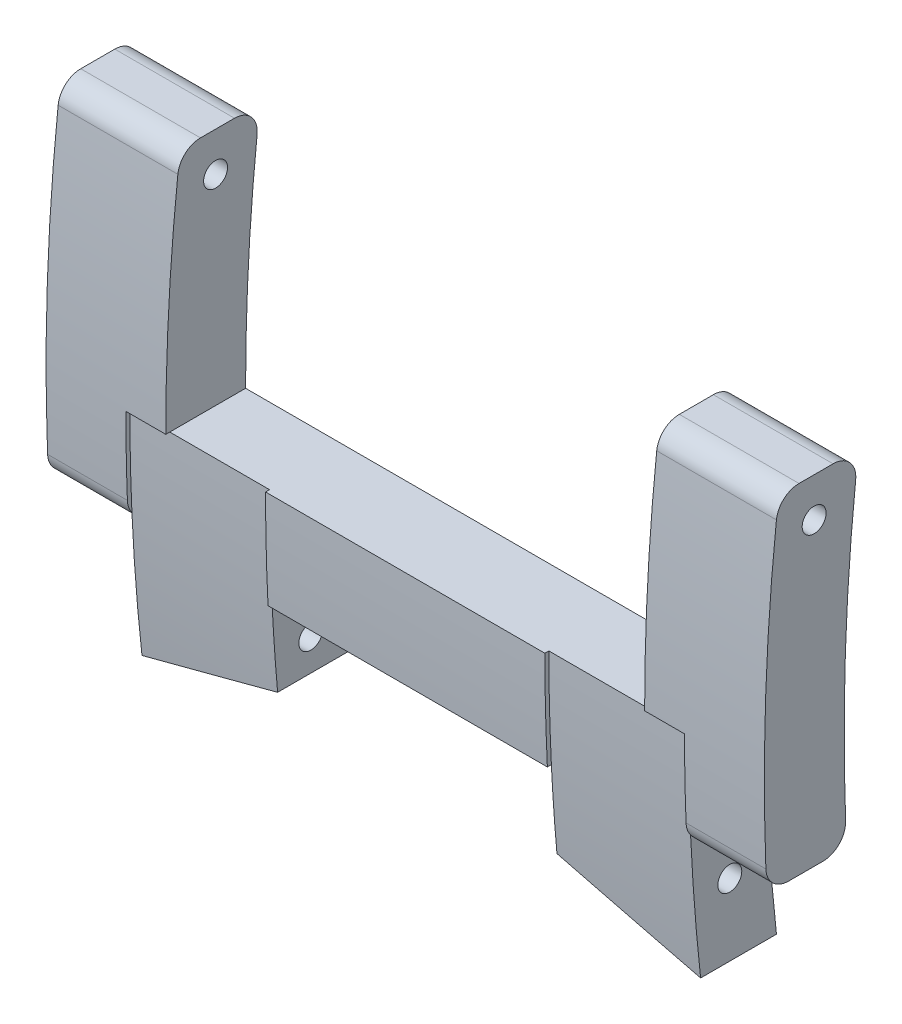
SolidWorks part; units mm, degrees
ref_plane "Front Plane" through (0, 0, 0) normal (0, 0, 1) x (1, 0, 0)
ref_plane "Top Plane" through (0, 0, 0) normal (0, 1, 0) x (1, 0, 0)
ref_plane "Right Plane" through (0, 0, 0) normal (1, 0, 0) x (0, 0, -1)
sketch "Sketch1" plane through (0, 0, 0) normal (0, 0, 1) x (1, 0, 0)
  line L0 (0, 0) -> (0, 8.5)
  line L1 (0, 8.5) -> (3, 8.5)
  line L2 (3, 8.5) -> (3, 2.5)
  line L3 (3, 2.5) -> (15, 2.5)
  line L8 (15, 2.5) -> (15, 8.5)
  line L9 (15, 8.5) -> (18, 8.5)
  line L10 (18, 8.5) -> (18, 0)
  line L11 (18, 0) -> (16, 0)
  line L12 (16, 0) -> (16, -3)
  line L13 (16, -3) -> (12.5, -2)
  line L14 (12.5, -2) -> (12.5, 0)
  line L15 (5.5, -2) -> (2, -3)
  line L16 (2, -3) -> (2, 0)
  line L17 (2, 0) -> (0, 0)
  line L18 (12.5, 0) -> (5.5, 0)
  line L19 (5.5, 0) -> (5.5, -2)
  dimension "D2" = 3
  dimension "D3" = 3
  dimension "D4" = 8.5
  dimension "D5" = 2.5
  dimension "D6" = 2
  dimension "D7" = 3.5
  dimension "D8" = 7
  dimension "D9" = 3.5
  dimension "D10" = 2
  dimension "D15" = 3
  dimension "D16" = 2
  dimension "D17" = 3
  dimension "D18" = 8.5
extrude "Boss-Extrude2" add sketch "Sketch1" along normal blind 5
sketch "Sketch8" plane through (0, 0, 0) normal (1, 0, 0) x (0, 0, -1)
  line L0 (0, 8.5) -> (0, 0) construction
  circle A0 centre (49, 2.5) radius 50
  dimension "D1" = 2.5
  dimension "D2" = 49
extrude "Cut-Extrude6" cut sketch "Sketch8" along normal blind 20
sketch "Sketch9" plane through (0, 0, 0) normal (1, 0, 0) x (0, 0, -1)
  circle A0 centre (47.1, 2.5) radius 50
  dimension "D1" = 2.5
  dimension "D2" = 47.1
extrude "Cut-Extrude7" cut sketch "Sketch9" along normal blind 20 flip side to cut
ref_plane "Plane1" through (0, 0, 4) normal (0, 0, 1) x (1, 0, 0)
sketch "Sketch11" plane through (0, 0, 4) normal (0, 0, 1) x (1, 0, 0)
  line L0 (0, 0) -> (0, 8.5)
  line L1 (0, 8.5) -> (3, 8.5)
  line L2 (3, 8.5) -> (3, 2.5)
  line L3 (2, 0) -> (0, 0)
  line L4 (5.5, 0) -> (5.5, 2.5)
  line L5 (3, 2.5) -> (15, 2.5) construction
  line L6 (12.5, 0) -> (5.5, 0)
  line L7 (5.5, 2.5) -> (12.5, 2.5)
  line L8 (18, 8.5) -> (15, 8.5)
  line L9 (18, 8.5) -> (18, 0)
  line L10 (18, 0) -> (16, 0)
  line L11 (15, 8.5) -> (15, 2.5)
  line L12 (12.5, 2.5) -> (12.5, 0)
  line L13 (3, 2.5) -> (2, 2.5)
  line L14 (2, 2.5) -> (2, 0)
  line L15 (15, 2.5) -> (16, 2.5)
  line L16 (16, 2.5) -> (16, 0)
extrude "Boss-Extrude4" add sketch "Sketch11" against normal blind 2
sketch "Sketch12" plane through (0, 0, 0) normal (1, 0, 0) x (0, 0, -1)
  circle A0 centre (47, 2.5) radius 50
  dimension "D1" = 2.5
  dimension "D2" = 47
extrude "Cut-Extrude8" cut sketch "Sketch12" along normal blind 20 flip side to cut
sketch "Sketch13" plane through (0, 0, 0) normal (1, 0, 0) x (0, 0, -1)
  line L0 (-2.6387, 8.5) -> (-0.6387, 8.5) construction
  circle A0 centre (-1.7523, 7.52) radius 0.3
  arc A1 (-0.6387, 8.5) -> (-0.9375, 0) centre (49, 2.5) ccw construction
  dimension "D1" = 0.98
  dimension "D2" = 51
extrude "Cut-Extrude10" cut sketch "Sketch13" along normal through all
sketch "Sketch14" plane through (0, 0, 0) normal (1, 0, 0) x (0, 0, -1)
  line L0 (-2.5966, -3) -> (-0.6966, -3) construction
  circle A0 centre (-1.8656, -1.2) radius 0.3
  arc A1 (-0.9375, 0) -> (-0.6966, -3) centre (49, 2.5) ccw construction
  dimension "D1" = 1.8
  dimension "D2" = 51
extrude "Cut-Extrude11" cut sketch "Sketch14" along normal blind 20
fillet "Fillet1" radius 0.57 8 edges at (1, 0, 0.9375) (1, 0, 2.9375) (17, 0, 0.9375) (17, 0, 2.9375) (16.5, 8.5, 2.6387) (16.5, 8.5, 0.6387) (1.5, 8.5, 0.6387) (1.5, 8.5, 2.6387)
